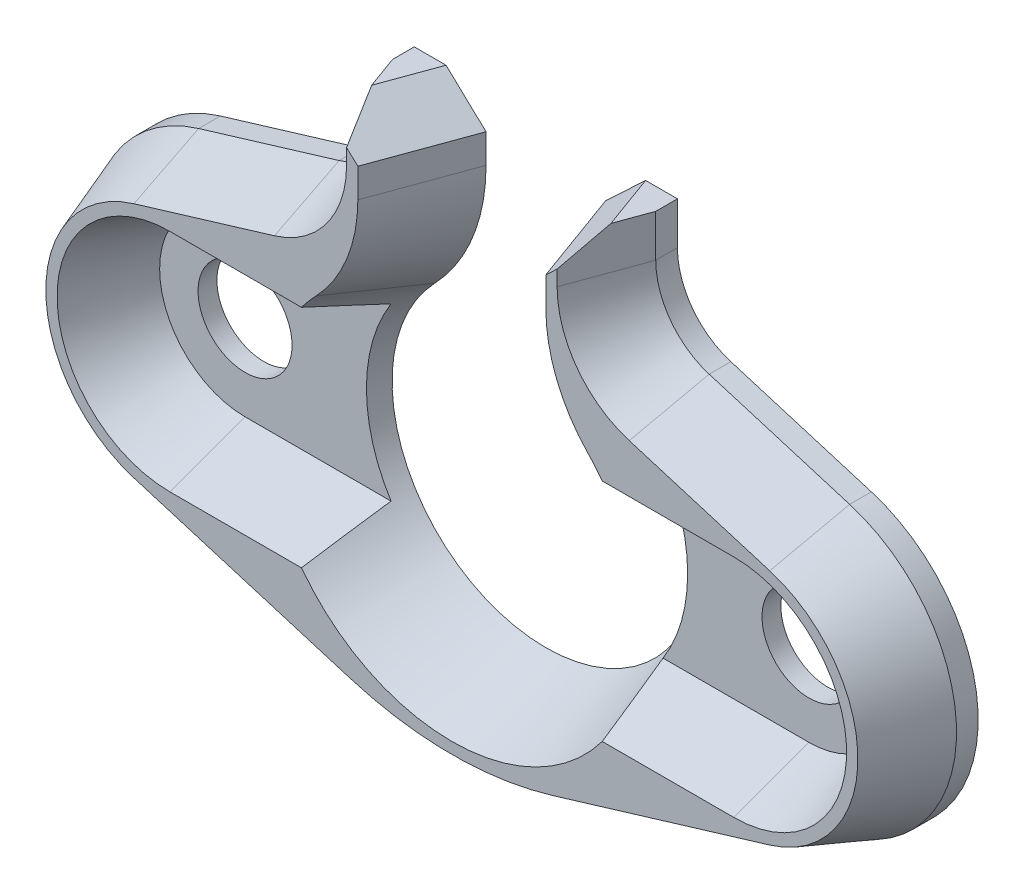
SolidWorks part; units mm, degrees
ref_plane "Front Plane" through (0, 0, 0) normal (0, 0, 1) x (1, 0, 0)
ref_plane "Top Plane" through (0, 0, 0) normal (0, 1, 0) x (1, 0, 0)
ref_plane "Right Plane" through (0, 0, 0) normal (1, 0, 0) x (0, 0, -1)
sketch "Sketch1" plane through (0, 0, 0) normal (0, 0, 1) x (1, 0, 0)
  line L0 (0, 20.6643) -> (0, -8.1469) construction
  line L9 (8.658, -3.8287) -> (2.8951, -5.5718)
  line L10 (-2.8951, -5.5718) -> (-8.658, -3.8287)
  line L13 (-1.5, 8) -> (-1.5, 6.2249)
  line L14 (3.5, 8) -> (1.5, 8)
  line L15 (1.5, 8) -> (1.5, 6.2249)
  line L16 (3.5, 8) -> (3.5, 6.8734)
  line L17 (8.658, 3.8287) -> (4.921, 4.959)
  line L18 (0, 0) -> (12.4882, 0) construction
  line L19 (-8.658, 3.8287) -> (-4.921, 4.959)
  line L20 (-3.5, 8) -> (-3.5, 6.8734)
  line L21 (-3.5, 8) -> (-1.5, 8)
  circle A0 centre (7.5, 0) radius 1.25
  circle A1 centre (-7.5, 0) radius 1.25
  arc A3 (2.8951, -5.5718) -> (-2.8951, -5.5718) centre (0, 4) cw
  arc A5 (8.658, 3.8287) -> (8.658, -3.8287) centre (7.5, 0) cw
  arc A6 (-2.8889, 2.7666) -> (2.8889, 2.7666) centre (0, 0) ccw
  arc A7 (-2.8889, 2.7666) -> (-1.5, 6.2249) centre (-6.5, 6.2249) ccw
  arc A8 (2.8889, 2.7666) -> (1.5, 6.2249) centre (6.5, 6.2249) cw
  arc A10 (4.921, 4.959) -> (3.5, 6.8734) centre (5.5, 6.8734) cw
  arc A11 (-8.658, 3.8287) -> (-8.658, -3.8287) centre (-7.5, 0) ccw
  arc A12 (-4.921, 4.959) -> (-3.5, 6.8734) centre (-5.5, 6.8734) ccw
  point P8 (0, 6.2587)
  point P20 (0, -6.4474)
  dimension "D2" = 2.5
  dimension "D3" = 8
  dimension "D4" = 10
  dimension "D5" = 4
  dimension "D6" = 4
  dimension "D7" = 8
  dimension "D10" = 5
  dimension "D9" = 2
  dimension "D1" = 15
  dimension "D8" = 3
  dimension "D11" = 2
extrude "Boss-Extrude1" add sketch "Sketch1" along normal blind 2.5
chamfer "Chamfer1" distance 1 angle 70 5 edges at (-1.5, 7.1125, 2.5) (-1.8602, 4.3616, 2.5) (0, -4, 2.5) (1.8602, 4.3616, 2.5) (1.5, 7.1125, 2.5) first distance on face at (0, 3.0317, 2.5)
sketch "Sketch2" plane through (0, 0, 2.5) normal (0, 0, 1) x (1, 0, 0)
  line L0 (-7.5, 2) -> (7.5, 2)
  line L1 (-7.5, -2) -> (7.5, -2)
  arc A0 (-7.5, 2) -> (-7.5, -2) centre (-7.5, 0) ccw
  arc A1 (7.5, -2) -> (7.5, 2) centre (7.5, 0) ccw
  dimension "D1" = 4
  dimension "D2" = 4
extrude "Cut-Extrude1" cut sketch "Sketch2" against normal blind 2
chamfer "Chamfer2" distance 1 angle 70 6 edges at (-6.0413, -2, 2.5) (-9.5, 0, 2.5) (-6.0413, 2, 2.5) (6.0413, -2, 2.5) (9.5, 0, 2.5) (6.0413, 2, 2.5) first distance on face at (0, 2.3023, 2.5)
chamfer "Chamfer3" distance 0.7 angle 70 11 edges at (3.5, 7.4367, 2.5) (3.8941, 5.6813, 2.5) (6.7895, 4.3939, 2.5) (11.5, 0, 2.5) (5.7765, -4.7002, 2.5) (0, -6, 2.5) (-5.7765, -4.7002, 2.5) (-11.5, 0, 2.5) (-6.7895, 4.3939, 2.5) (-3.8941, 5.6813, 2.5) (-3.5, 7.4367, 2.5) first distance on face at (0, 2.3379, 2.5)
chamfer "Chamfer4" distance 1 angle 45 2 edges at (-2.045, 8, 1.25) (2.045, 8, 1.25)
